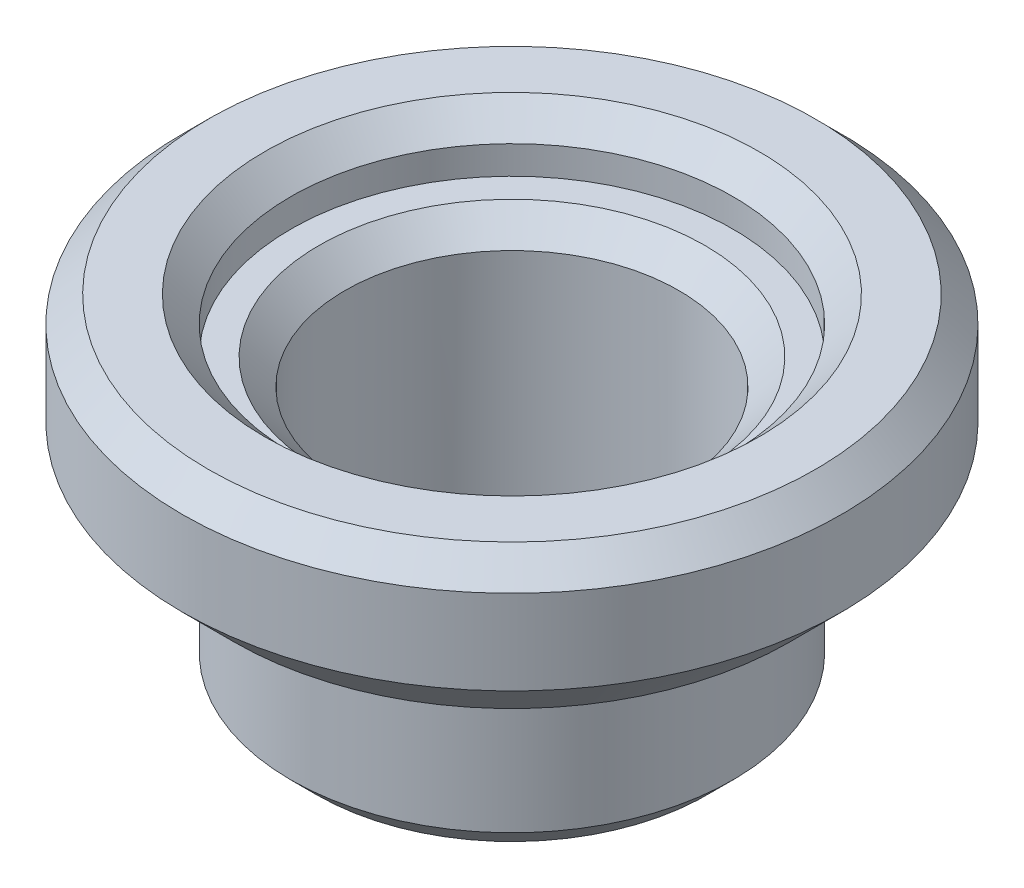
SolidWorks part; units mm, degrees
material "PET"
ref_plane "Front Plane" through (0, 0, 0) normal (0, 0, 1) x (1, 0, 0)
ref_plane "Top Plane" through (0, 0, 0) normal (0, 1, 0) x (1, 0, 0)
ref_plane "Right Plane" through (0, 0, 0) normal (1, 0, 0) x (0, 0, -1)
sketch "Sketch1" plane through (0, 0, 0) normal (0, 1, 0) x (1, 0, 0)
  circle A0 centre (0, 0) radius 9.652
  circle A1 centre (0, 0) radius 6.477
  dimension "D1" = 12.954
  dimension "D2" = 3.175
extrude "Boss-Extrude1" add sketch "Sketch1" along normal blind 3.175 contours A1 | A0 A1 region at (-9.379, 0, 0) region at (0, 0, 0)
extrude "Boss-Extrude2" add sketch "Sketch1<3>" along normal blind 1.5875 from surface contours A0 A1 region at (-9.379, 0, 0) starting at face at (0, 3.175, 9.652)
sketch "Sketch1<3>" plane through (0, 0, 0) normal (0, 1, 0) x (1, 0, 0) same geometry as "Sketch1"
sketch "Sketch2" plane through (0, 0, 0) normal (0, -1, 0) x (1, 0, 0)
  circle A0 centre (0, 0) radius 6.477
  circle A1 centre (0, 0) radius 4.8895
  dimension "D1" = 12.954
  dimension "D2" = 9.779
extrude "Boss-Extrude3" add sketch "Sketch2" along normal blind 5.08
sketch "Sketch3" plane through (0, 0, 0) normal (0, -1, 0) x (1, 0, 0)
  circle A1 centre (0, 0) radius 4.8895
  circle A2 centre (0, 0) radius 4.8895
  dimension "D1" = 0
extrude "Cut-Extrude1" cut sketch "Sketch3" against normal through all
chamfer "Chamfer1" distance 1.524 angle 45 1 edges at (0, 0, 9.652)
chamfer "Chamfer2" distance 0.762 angle 45 3 edges at (0, 4.7625, 6.477) (0, 4.7625, 9.652) (0, 3.175, 4.8895)
chamfer "Chamfer3" distance 0.762 angle 45 1 edges at (0, -5.08, -6.477)
